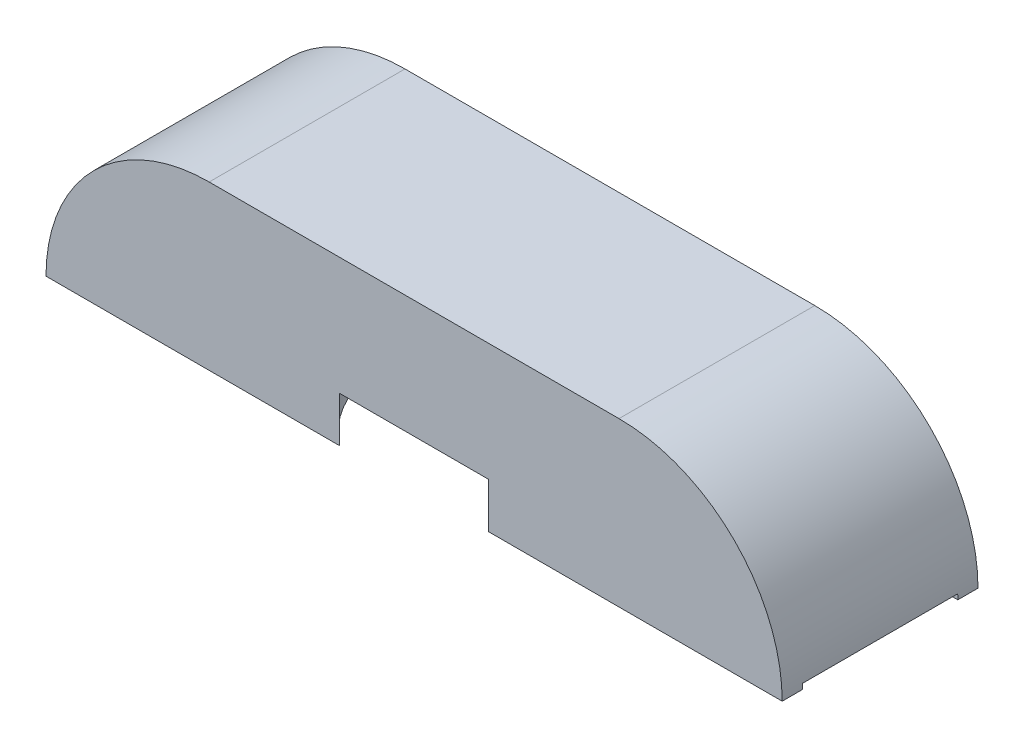
SolidWorks part; units mm, degrees
ref_plane "Front Plane" through (0, 0, 0) normal (0, 0, 1) x (1, 0, 0)
ref_plane "Top Plane" through (0, 0, 0) normal (0, 1, 0) x (1, 0, 0)
ref_plane "Right Plane" through (0, 0, 0) normal (1, 0, 0) x (0, 0, -1)
sketch "Sketch1" plane through (0, 0, 0) normal (0, 1, 0) x (1, 0, 0)
  line L1 (-45.115, 12) -> (45.115, 12)
  line L2 (-45.115, 12) -> (-45.115, -12)
  line L3 (-45.115, -12) -> (45.115, -12)
  line L4 (45.115, 12) -> (45.115, -12)
  line L5 (-45.115, 12) -> (45.115, -12) construction
  line L6 (-45.115, -12) -> (45.115, 12) construction
  point P0 (0, 0)
  point P13 (45.115, 0)
  dimension "D1" = 90.23
  dimension "D2" = 24
extrude "Boss-Extrude1" add sketch "Sketch1" along normal blind 20
fillet "Fillet1" radius 20 2 edges at (45.115, 20, 0) (-45.115, 20, 0)
sketch "Sketch2" plane through (0, 0, 0) normal (0, -1, 0) x (1, 0, 0)
  line L0 (45.115, 12) -> (45.115, -12) construction
  line L1 (45.115, 9.525) -> (38.635, 9.525)
  line L2 (45.115, 9.525) -> (45.115, -9.525)
  line L3 (45.115, -9.525) -> (38.635, -9.525)
  line L4 (38.635, 9.525) -> (38.635, -9.525)
  point P6 (38.635, 0)
  dimension "D1" = 19.05
  dimension "D2" = 6.48
extrude "Cut-Extrude1" cut sketch "Sketch2" against normal blind 0.64
hole_wizard "M2 Clearance Hole1" positions "Sketch3" profile "Sketch4" hole size "M2" standard "ANSI Metric"
sketch "Sketch3" plane through (0, 0.64, 0) normal (0, -1, 0) x (-1, 0, 0)
  line L0 (-41.875, 5.565) -> (-41.875, -5.565) construction
  line L2 (-38.635, 9.525) -> (-45.115, 9.525) construction
  point P0 (-41.875, 5.565)
  point P2 (-41.875, -5.565)
  point P9 (-41.875, 0)
  point P13 (-41.875, 9.525)
  dimension "D1" = 11.13
sketch "Sketch4" plane through (41.875, 0.64, -5.565) normal (1, 0, 0) x (0, 0, -1)
  line L0 (0, 0) -> (0, 2.7811)
  line L1 (0, 2.7811) -> (1.3, 2)
  line L2 (1.3, 2) -> (1.3, 0)
  line L5 (1.3, 0) -> (0, 0)
  line L10 (0, 2.7811) -> (-1.3, 2) construction
  line L11 (0, -6.35) -> (0, 107.95) construction
  dimension "Hole Dia." = 2.6
  dimension "Hole Depth" = 2
  dimension "Drill Angle" = 118
sketch "Sketch5" plane through (0, 0, 0) normal (0, -1, 0) x (1, 0, 0)
  circle A0 centre (0, 0) radius 15.08
  dimension "D1" = 30.16
extrude "Cut-Extrude2" cut sketch "Sketch5" against normal blind 5.56
sketch "Sketch6" plane through (0, 5.56, 0) normal (0, -1, 0) x (1, 0, 0)
  circle A0 centre (0, 0) radius 11.905
  dimension "D1" = 23.81
extrude "Cut-Extrude3" cut sketch "Sketch6" against normal blind 11.1
